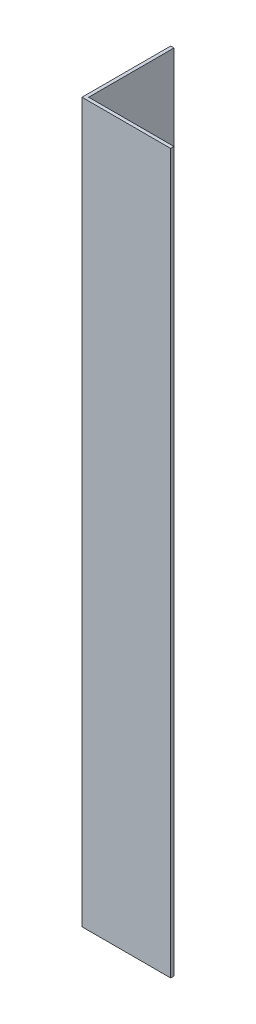
SolidWorks part; units mm, degrees
material "1060 Сплав"
ref_plane "Спереди" through (0, 0, 0) normal (0, 0, 1) x (1, 0, 0)
ref_plane "Сверху" through (0, 0, 0) normal (0, 1, 0) x (1, 0, 0)
ref_plane "Справа" through (0, 0, 0) normal (1, 0, 0) x (0, 0, -1)
sketch "Эскиз1" plane through (0, 0, 0) normal (0, 1, 0) x (1, 0, 0)
  line L0 (0, 0) -> (0, 20)
  line L1 (0, 20) -> (0.75, 20)
  line L2 (0.75, 20) -> (0.75, 0.75)
  line L3 (0.75, 0.75) -> (20, 0.75)
  line L4 (20, 0.75) -> (20, 0)
  line L5 (20, 0) -> (0, 0)
  dimension "D1" = 0.75
  dimension "D2" = 20
extrude "Бобышка-Вытянуть1" add sketch "Эскиз1" along normal blind 162
